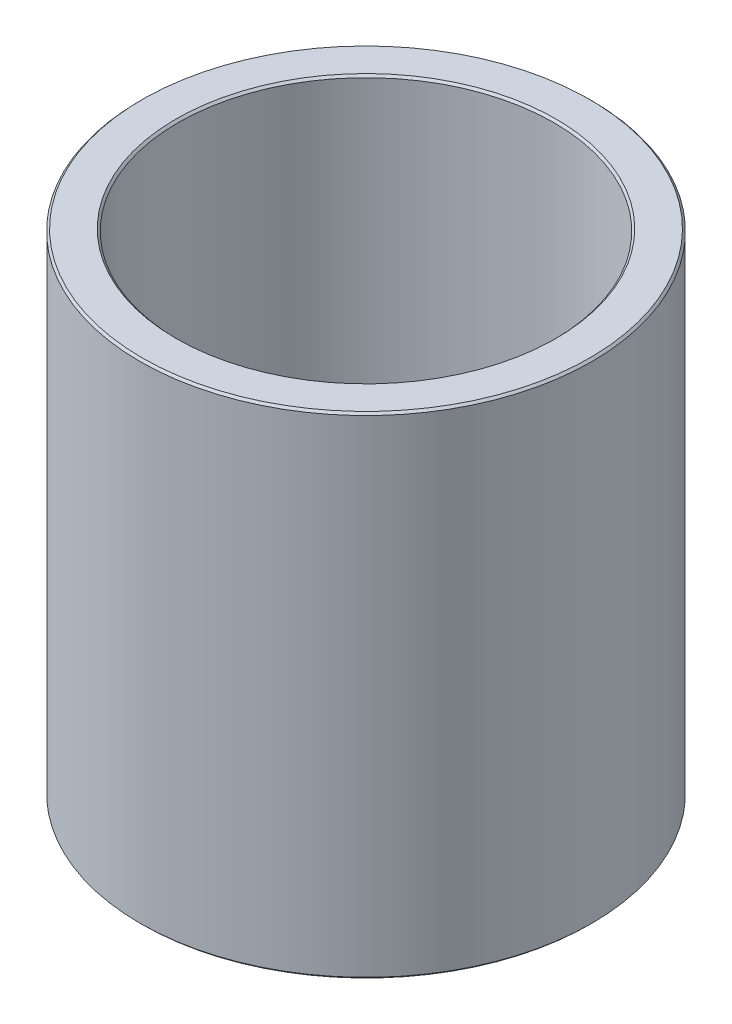
SolidWorks part; units mm, degrees
ref_plane "Front Plane" through (0, 0, 0) normal (0, 0, 1) x (1, 0, 0)
ref_plane "Top Plane" through (0, 0, 0) normal (0, 1, 0) x (1, 0, 0)
ref_plane "Right Plane" through (0, 0, 0) normal (1, 0, 0) x (0, 0, -1)
sketch "Sketch1" plane through (0, 0, 0) normal (0, 1, 0) x (1, 0, 0)
  circle A0 centre (0, 0) radius 45
  dimension "SLEEVE_OD" = 90
extrude "Boss-Extrude1" add sketch "Sketch1" along normal blind 97.7543
sketch "Sketch2" plane through (0, 0, 0) normal (0, 1, 0) x (1, 0, 0)
  circle A0 centre (0, 0) radius 37.4405
  dimension "BORE_D" = 74.881
extrude "Cut-Extrude1" cut sketch "Sketch2" along normal through all
chamfer "Chamfer1" distance 0.4185 angle 45 4 edges at (0, 97.7543, 37.4405) (0, 0, 37.4405) (0, 0, 45) (0, 97.7543, 45)
